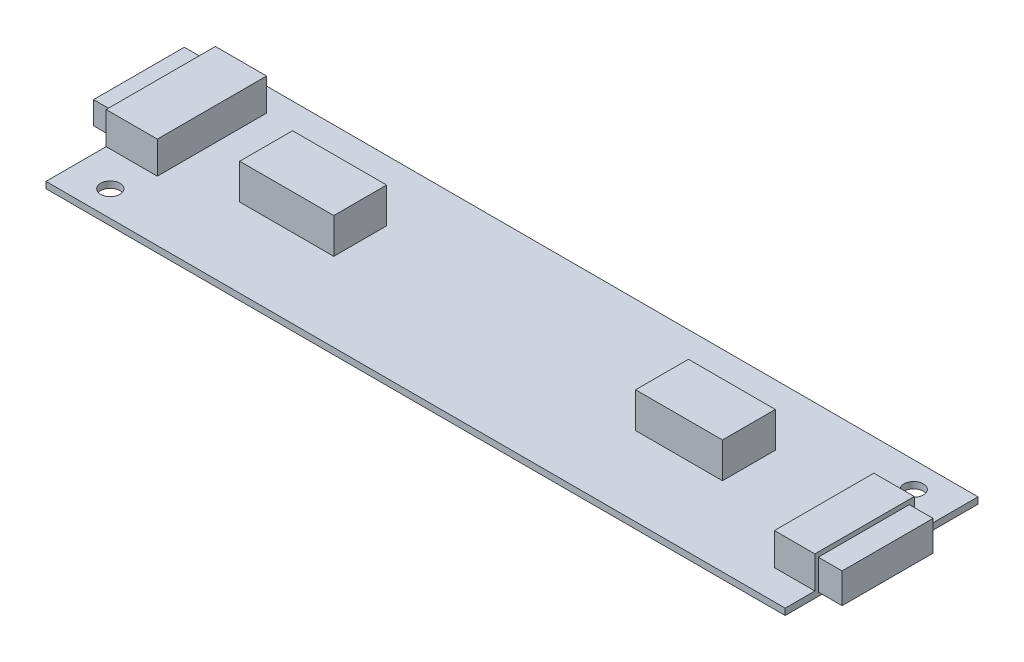
SolidWorks part; units mm, degrees
ref_plane "Front Plane" through (0, 0, 0) normal (0, 0, 1) x (1, 0, 0)
ref_plane "Top Plane" through (0, 0, 0) normal (0, 1, 0) x (1, 0, 0)
ref_plane "Right Plane" through (0, 0, 0) normal (1, 0, 0) x (0, 0, -1)
sketch "Sketch1" plane through (0, 0, 0) normal (0, 1, 0) x (1, 0, 0)
  line L1 (0, 0) -> (115, 0)
  line L2 (0, 0) -> (0, -30)
  line L3 (0, -30) -> (115, -30)
  line L4 (115, 0) -> (115, -30)
  dimension "D1" = 115
  dimension "D2" = 30
extrude "Extrude1" add sketch "Sketch1" along normal blind 1
sketch "Sketch2" plane through (0, 1, 0) normal (0, 1, 0) x (-1, 0, 0)
  line L0 (0, 30) -> (-115, 30) construction
  line L1 (0, 0) -> (0, 30) construction
  circle A0 centre (-109, 4) radius 1.5
  circle A1 centre (-6, 26) radius 1.5
  dimension "D1" = 3
  dimension "D2" = 3
  dimension "D3" = 4
  dimension "D4" = 6
  dimension "D5" = 26
  dimension "D6" = 109
extrude "mount holes - cut" cut sketch "Sketch2" against normal blind 1
sketch "Sketch4" plane through (0, 1, 0) normal (0, 1, 0) x (-1, 0, 0)
  line L1 (-92.9629, 9.4959) -> (-79.4466, 9.4959)
  line L2 (-92.9629, 9.4959) -> (-92.9629, 17.7172)
  line L3 (-92.9629, 17.7172) -> (-79.4466, 17.7172)
  line L4 (-79.4466, 9.4959) -> (-79.4466, 17.7172)
  line L5 (-32.4879, 9.4959) -> (-17.8568, 9.4959)
  line L6 (-32.4879, 9.4959) -> (-32.4879, 17.7172)
  line L7 (-32.4879, 17.7172) -> (-17.8568, 17.7172)
  line L8 (-17.8568, 9.4959) -> (-17.8568, 17.7172)
extrude "inductors" add sketch "Sketch4" along normal blind 5.5
sketch "Sketch5" plane through (0, 1, 0) normal (0, 1, 0) x (-1, 0, 0)
  line L0 (-115, 30) -> (-115, 0) construction
  line L1 (-115, 9.914) -> (-108.7087, 9.914)
  line L2 (-115, 9.914) -> (-115, 25.3811)
  line L3 (-115, 25.3811) -> (-108.7087, 25.3811)
  line L4 (-108.7087, 9.914) -> (-108.7087, 25.3811)
  line L5 (0, 0) -> (0, 30) construction
  line L6 (-7.9635, 3.6435) -> (0, 3.6435)
  line L7 (-7.9635, 3.6435) -> (-7.9635, 20.6434)
  line L8 (-7.9635, 20.6434) -> (0, 20.6434)
  line L9 (0, 3.6435) -> (0, 20.6434)
extrude "ccfl conn" add sketch "Sketch5" along normal blind 5
sketch "Sketch6" plane through (115, 0, 0) normal (1, 0, 0) x (0, 0, -1)
  line L1 (-24.8452, 5.2864) -> (-10.6883, 5.2864)
  line L2 (-24.8452, 5.2864) -> (-24.8452, 0.5956)
  line L3 (-24.8452, 0.5956) -> (-10.6883, 0.5956)
  line L4 (-10.6883, 5.2864) -> (-10.6883, 0.5956)
extrude "mate stick-out 1" add sketch "Sketch6" along normal blind 3.7
sketch "Sketch7" plane through (0, 0, 0) normal (-1, 0, 0) x (0, 0, 1)
  line L1 (4.7831, 4.6156) -> (18.9002, 4.6156)
  line L2 (4.7831, 4.6156) -> (4.7831, 1.0835)
  line L3 (4.7831, 1.0835) -> (18.9002, 1.0835)
  line L4 (18.9002, 4.6156) -> (18.9002, 1.0835)
extrude "mate stick-out 2" add sketch "Sketch7" along normal blind 3.7
